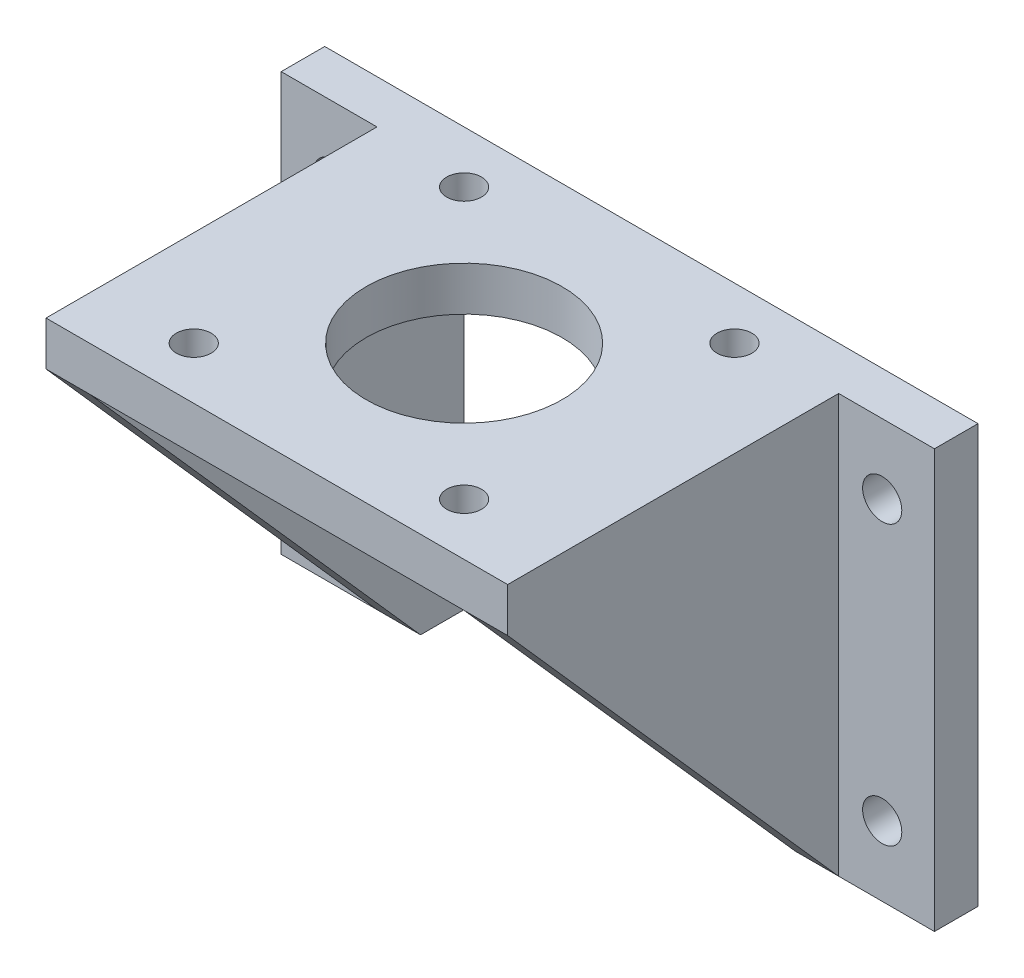
SolidWorks part; units mm, degrees
material "Copper"
ref_plane "Front Plane" through (0, 0, 0) normal (0, 0, 1) x (1, 0, 0)
ref_plane "Top Plane" through (0, 0, 0) normal (0, 1, 0) x (1, 0, 0)
ref_plane "Right Plane" through (0, 0, 0) normal (1, 0, 0) x (0, 0, -1)
sketch "Sketch1" plane through (0, 0, 0) normal (0, 0, 1) x (1, 0, 0)
  line L0 (0, 0) -> (0, 43)
  line L1 (0, 43) -> (43, 43)
  line L2 (43, 43) -> (43, 0)
  line L3 (43, 0) -> (59, 0)
  line L4 (59, 0) -> (59, 48)
  line L5 (59, 48) -> (-16, 48)
  line L6 (-16, 48) -> (-16, 0)
  line L7 (-16, 0) -> (0, 0)
  circle A0 centre (-10, 40) radius 2.25
  circle A1 centre (53, 40) radius 2.25
  circle A2 centre (53, 8) radius 2.25
  circle A3 centre (-10, 8) radius 2.25
  dimension "D5" = 8
  dimension "D1" = 16
  dimension "D2" = 16
  dimension "D3" = 5
  dimension "D4" = 43
  dimension "D6" = 6
  dimension "D7" = 2
  dimension "D8" = 2
extrude "Boss-Extrude1" add sketch "Sketch1" along normal blind 5
sketch "Sketch2" plane through (0, 0, 5) normal (0, 0, 1) x (1, 0, 0)
  line L1 (59, 48) -> (-16, 48) construction
  line L2 (-5, 42.9307) -> (48, 42.9307)
  line L3 (-5, 42.9307) -> (-5, 48)
  line L4 (-5, 48) -> (48, 48)
  line L5 (48, 42.9307) -> (48, 48)
  line L6 (0, 0) -> (0, 43) construction
  line L7 (43, 43) -> (43, 0) construction
  dimension "D1" = 5
  dimension "D2" = 5
extrude "Boss-Extrude2" add sketch "Sketch2" along normal blind 38
ref_plane "Plane1" through (-5, 0, 0) normal (-1, 0, 0) x (0, 0, 1)
sketch "Sketch3" plane through (-5, 0, 0) normal (-1, 0, 0) x (0, 0, 1)
  line L0 (5, 48) -> (5, 0)
  line L1 (43, 48) -> (5, 48) construction
  line L2 (5, 48) -> (5, 42.9307) construction
  line L3 (5, 0) -> (43, 42.9307)
  line L4 (43, 42.9307) -> (43, 48)
  line L5 (43, 48) -> (5, 48)
extrude "Boss-Extrude3" add sketch "Sketch3" against normal blind 5
ref_plane "Plane2" through (48, 0, 0) normal (1, 0, 0) x (0, 0, -1)
sketch "Sketch4" plane through (48, 0, 0) normal (1, 0, 0) x (0, 0, -1)
  line L0 (-43, 48) -> (-43, 42.9307)
  line L1 (-43, 42.9307) -> (-5, 0)
  line L2 (-5, 0) -> (-5, 48)
  line L3 (-5, 48) -> (-43, 48)
extrude "Boss-Extrude4" add sketch "Sketch4" against normal blind 5
sketch "Sketch5" plane through (0, 48, 0) normal (0, 1, 0) x (1, 0, 0)
  line L0 (-5, 20.9) -> (-5, -20.9) construction
  line L1 (48, -20.9) -> (48, 20.9) construction
  line L2 (59, 0) -> (-16, 0) construction
  line L3 (48, -43) -> (-5, -43) construction
  circle A0 centre (21.5, -21.5) radius 11.25
  circle A1 centre (5.98, -5.98) radius 2
  circle A2 centre (37.02, -5.98) radius 2
  circle A3 centre (37.02, -37.02) radius 2
  circle A4 centre (5.98, -37.02) radius 2
  dimension "D1" = 22.5
  dimension "D6" = 15.52
  dimension "D2" = 26.5
  dimension "D3" = 26.5
  dimension "D4" = 21.5
  dimension "D5" = 21.5
  dimension "D7" = 15.52
  dimension "D8" = 2
  dimension "D9" = 2
extrude "Cut-Extrude1" cut sketch "Sketch5" against normal through all
